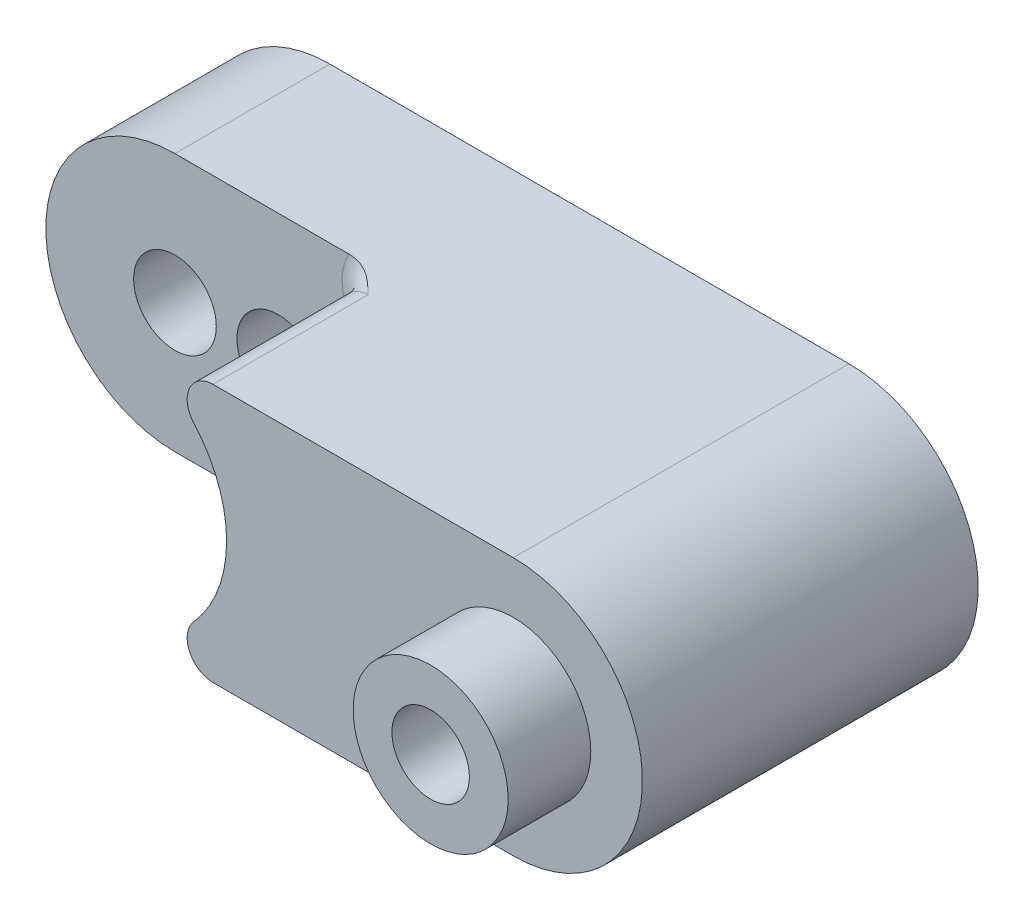
SolidWorks part; units mm, degrees
ref_plane "Top Plane" through (0, 0, 0) normal (0, 0, 1) x (1, 0, 0)
ref_plane "Right Plane" through (0, 0, 0) normal (0, 1, 0) x (1, 0, 0)
ref_plane "Front Plane" through (0, 0, 0) normal (1, 0, 0) x (0, 0, -1)
sketch "Sketch1" plane through (0, 0, 0) normal (0, 0, 1) x (1, 0, 0)
  line L0 (0, 0) -> (20.1, 0) construction
  line L1 (0, 0) -> (-19.9, 0) construction
  line L2 (0, 0) -> (20.1, 0) construction
  line L3 (0, 5) -> (20.1, 5)
  line L4 (0, -5) -> (20.1, -5)
  circle A0 centre (0, 0) radius 1.5 construction
  circle A1 centre (4, 0) radius 1.5 construction
  circle A2 centre (20.1, 0) radius 1.5
  arc A3 (0, 5) -> (0, -5) centre (0, 0) ccw
  arc A4 (20.1, -5) -> (20.1, 5) centre (20.1, 0) ccw
  point P5 (10.05, 0)
  dimension "D1" = 4
  dimension "D2" = 3
  dimension "D3" = 3
  dimension "D4" = 19.9
  dimension "D5" = 40
  dimension "D6" = 10
extrude "Boss-Extrude1" add sketch "Sketch1" along normal mid plane 6
sketch "Sketch2" plane through (0, 0, 3) normal (0, 0, 1) x (1, 0, 0)
  line L0 (4, 0) -> (20.1, 0) construction
  line L2 (0, -5) -> (20.1, -5)
  line L3 (20.1, 5) -> (0, 5)
  line L4 (4, -5) -> (20.1, -5)
  line L5 (20.1, 5) -> (4, 5)
  arc A0 (4, -5) -> (4, 5) centre (4, 0) ccw
  circle A1 centre (20.1, 0) radius 1.5 construction
  circle A2 centre (20.1, 0) radius 1.5
  arc A3 (0, 5) -> (0, -5) centre (0, 0) ccw
  arc A4 (20.1, -5) -> (20.1, 5) centre (20.1, 0) ccw
  arc A6 (20.1, -5) -> (20.1, 5) centre (20.1, 0) ccw
  dimension "D1" = 0
  dimension "D2" = 4
extrude "Boss-Extrude2" add sketch "Sketch2" along normal blind 7
fillet "Fillet1" radius 1 2 edges at (4, 5, 6.5) (4, -5, 6.5)
fillet "Fillet2" radius 1 3 edges at (7.5593, 4.4082, 3) (7.5593, -4.4082, 3) (9, 0, 3)
sketch "Sketch3" plane through (0, 0, 10) normal (0, 0, 1) x (1, 0, 0)
  circle A0 centre (20.1, 0) radius 1.5 construction
  circle A1 centre (20.1, 0) radius 1.5
  circle A2 centre (20.1, 0) radius 3
  dimension "D1" = 6
extrude "Boss-Extrude3" add sketch "Sketch3" along normal blind 3.2
sketch "Sketch4" plane through (0, 0, -3) normal (0, 0, -1) x (-1, 0, 0)
  line L1 (-20.1, 3.4641) -> (-23.1, 1.7321)
  line L2 (-23.1, 1.7321) -> (-23.1, -1.7321)
  line L3 (-23.1, -1.7321) -> (-20.1, -3.4641)
  line L4 (-20.1, -3.4641) -> (-17.1, -1.7321)
  line L5 (-17.1, -1.7321) -> (-17.1, 1.7321)
  line L6 (-17.1, 1.7321) -> (-20.1, 3.4641)
  circle A0 centre (-20.1, 0) radius 3 construction
  dimension "D1" = 6
extrude "Cut-Extrude1" cut sketch "Sketch4" against normal offset from surface (9 mm away) 4 up to face at (12.9651, 0, 10)
hole_wizard "CBORE for M3 Hex Socket Head Cap Screw1" positions "Sketch10" profile "Sketch11" counterbore size "M3" standard "ISO" end condition through all
sketch "Sketch10" plane through (0, 0, -3) normal (0, 0, -1) x (-1, 0, 0)
  point P0 (-4, 0)
sketch "Sketch11" plane through (4, 0, -3) normal (1, 0, 0) x (0, 1, 0)
  line L0 (0, 0) -> (0, 16.2)
  line L1 (0, 16.2) -> (1.6, 16.2)
  line L3 (1.6, 16.2) -> (1.6, 3.4)
  line L4 (1.6, 3.4) -> (3.25, 3.4)
  line L5 (3.25, 3.4) -> (3.25, 0)
  line L7 (3.25, 0) -> (0, 0)
  line L11 (0, -6.35) -> (0, 107.95) construction
  dimension "Thru Hole Dia." = 3.2
  dimension "Thru Hole Depth" = 16.2
  dimension "C'Bore Dia." = 6.5
  dimension "C'Bore Depth" = 3.4
hole_wizard "CBORE for M3 Hex Socket Head Cap Screw2" positions "Sketch12" profile "Sketch13" counterbore size "M3" standard "ISO" end condition through all
sketch "Sketch12" plane through (0, 0, -3) normal (0, 0, -1) x (-1, 0, 0)
  point P0 (0, 0)
sketch "Sketch13" plane through (0, 0, -3) normal (1, 0, 0) x (0, 1, 0)
  line L0 (0, 0) -> (0, 16.2)
  line L1 (0, 16.2) -> (1.6, 16.2)
  line L3 (1.6, 16.2) -> (1.6, 3.4)
  line L4 (1.6, 3.4) -> (3.25, 3.4)
  line L5 (3.25, 3.4) -> (3.25, 0)
  line L7 (3.25, 0) -> (0, 0)
  line L11 (0, -6.35) -> (0, 107.95) construction
  dimension "Thru Hole Dia." = 3.2
  dimension "Thru Hole Depth" = 16.2
  dimension "C'Bore Dia." = 6.5
  dimension "C'Bore Depth" = 3.4
